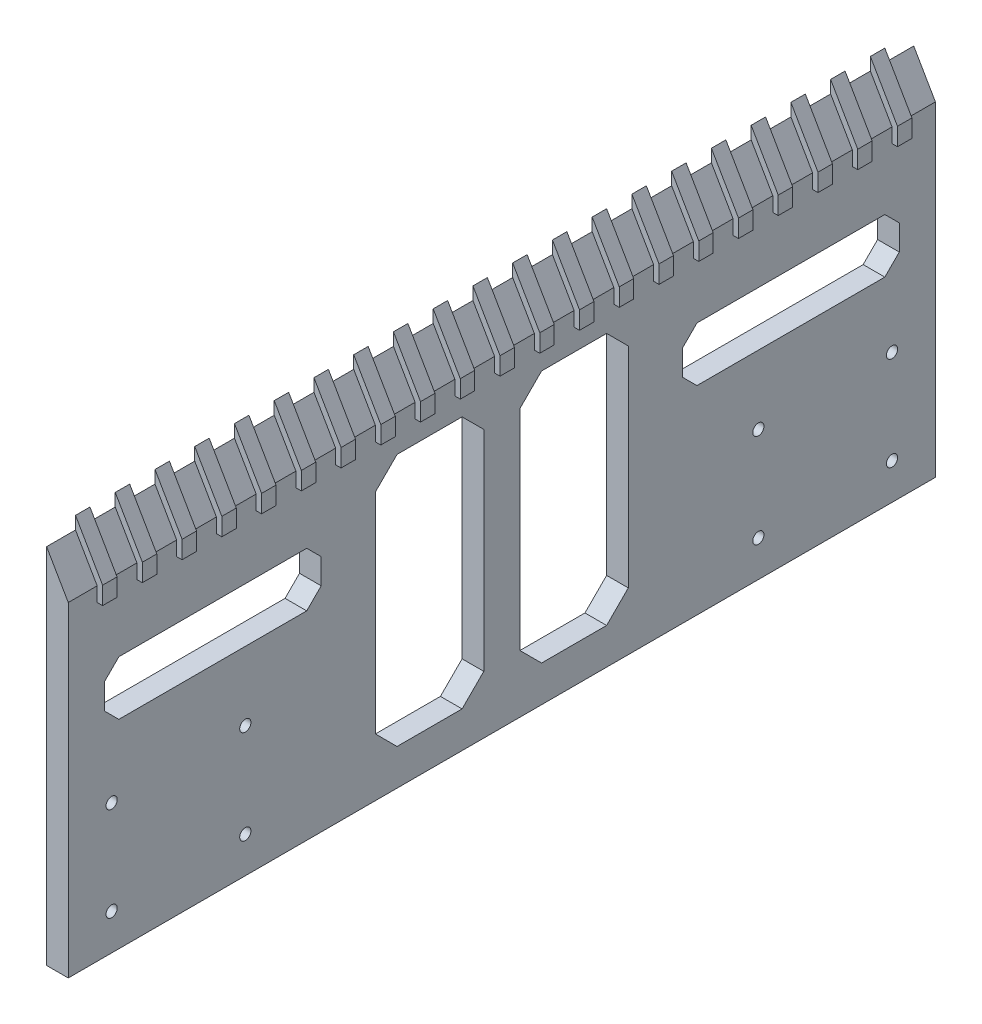
SolidWorks part; units mm, degrees
ref_plane "前视基准面" through (0, 0, 0) normal (0, 0, 1) x (1, 0, 0)
ref_plane "上视基准面" through (0, 0, 0) normal (0, 1, 0) x (1, 0, 0)
ref_plane "右视基准面" through (0, 0, 0) normal (1, 0, 0) x (0, 0, -1)
sketch "草图1" plane through (0, 0, 0) normal (1, 0, 0) x (0, 0, -1)
  line L1 (0, 0) -> (240, 0)
  line L2 (0, 0) -> (0, -90)
  line L3 (0, -90) -> (240, -90)
  line L4 (240, 0) -> (240, -90)
  dimension "D1" = 240
  dimension "D2" = 90
extrude "凸台-拉伸1" add sketch "草图1" along normal blind 6
sketch "草图2" plane through (6, 0, 0) normal (1, 0, 0) x (0, 0, -1)
  line L0 (0, 0) -> (0, -90) construction
  line L1 (12, -54) -> (49, -54) construction
  line L2 (12, -54) -> (12, -80) construction
  line L3 (12, -80) -> (49, -80) construction
  line L4 (49, -54) -> (49, -80) construction
  line L5 (240, 0) -> (0, 0) construction
  line L6 (120, 0) -> (120, -90) construction
  line L7 (0, -90) -> (240, -90) construction
  line L8 (191, -54) -> (191, -80) construction
  line L9 (228, -80) -> (191, -80) construction
  line L10 (228, -54) -> (228, -80) construction
  line L11 (228, -54) -> (191, -54) construction
  circle A0 centre (12, -54) radius 1.55
  circle A1 centre (49, -80) radius 1.55
  circle A2 centre (49, -54) radius 1.55
  circle A3 centre (12, -80) radius 1.55
  circle A4 centre (228, -80) radius 1.55
  circle A5 centre (191, -54) radius 1.55
  circle A6 centre (191, -80) radius 1.55
  circle A7 centre (228, -54) radius 1.55
  dimension "D5" = 3.1
  dimension "D1" = 12
  dimension "D2" = 54
  dimension "D3" = 37
  dimension "D4" = 26
extrude "切除-拉伸1" cut sketch "草图2" against normal through all
sketch "草图3" plane through (6, 0, 0) normal (1, 0, 0) x (0, 0, -1)
  line L0 (120, 0) -> (120, -90) construction
  line L1 (10, -20) -> (70, -20)
  line L2 (10, -20) -> (10, -35)
  line L3 (10, -35) -> (70, -35)
  line L4 (70, -20) -> (70, -35)
  line L5 (240, 0) -> (0, 0) construction
  line L6 (0, -90) -> (240, -90) construction
  line L7 (0, 0) -> (0, -90) construction
  line L8 (170, -20) -> (170, -35)
  line L9 (230, -35) -> (170, -35)
  line L10 (230, -20) -> (230, -35)
  line L11 (230, -20) -> (170, -20)
  dimension "D1" = 10
  dimension "D2" = 20
  dimension "D3" = 15
  dimension "D4" = 60
extrude "切除-拉伸2" cut sketch "草图3" against normal through all
sketch "草图4" plane through (6, 0, 0) normal (1, 0, 0) x (0, 0, -1)
  line L0 (120, 0) -> (120, -90) construction
  line L1 (85, -10) -> (115, -10)
  line L2 (85, -10) -> (85, -80)
  line L3 (85, -80) -> (115, -80)
  line L4 (115, -10) -> (115, -80)
  line L5 (240, 0) -> (0, 0) construction
  line L6 (0, -90) -> (240, -90) construction
  line L7 (0, 0) -> (0, -90) construction
  line L8 (125, -10) -> (125, -80)
  line L9 (155, -80) -> (125, -80)
  line L10 (155, -10) -> (155, -80)
  line L11 (155, -10) -> (125, -10)
  dimension "D1" = 10
  dimension "D2" = 70
  dimension "D3" = 85
  dimension "D4" = 30
extrude "切除-拉伸3" cut sketch "草图4" against normal through all contours L4 L1 L2 L3 | L8 L9 L10 L11 region at (6, -45, -100)
sketch "草图5" plane through (0, 0, 0) normal (-1, 0, 0) x (0, 0, 1)
  circle A0 centre (-191, -80) radius 3
  circle A1 centre (-228, -80) radius 3
  circle A2 centre (-191, -54) radius 3
  circle A3 centre (-228, -54) radius 3
  circle A4 centre (-45, -80) radius 3
  circle A5 centre (-12, -80) radius 3
  circle A6 centre (-12, -54) radius 3
  circle A7 centre (-49, -54) radius 3
  dimension "D1" = 6
extrude "切除-拉伸4" cut sketch "草图5" against normal blind 3
sketch "草图6" plane through (0, 0, 0) normal (0, 0, 1) x (1, 0, 0)
  line L0 (6, 0) -> (0, 0)
  line L1 (0, 0) -> (0, 10.3923)
  line L2 (0, 10.3923) -> (6, 0)
  dimension "D1" = 30
extrude "凸台-拉伸2" add sketch "草图6" against normal blind 240
ref_plane "基准面1" through (0, 0, -120) normal (0, 0, 1) x (1, 0, 0)
chamfer "倒角1" distance 4 angle 45 8 edges at (3, -35, -170) (3, -35, -230) (3, -20, -230) (3, -20, -170) (3, -35, -70) (3, -20, -70) (3, -35, -10) (3, -20, -10)
chamfer "倒角2" distance 6 angle 45 8 edges at (3, -80, -125) (3, -10, -155) (3, -10, -125) (3, -80, -155) (3, -80, -115) (3, -80, -85) (3, -10, -115) (3, -10, -85)
sketch "草图8" plane through (0, 0, -120) normal (0, 0, 1) x (1, 0, 0)
  line L0 (0, 10.3923) -> (0, 13.8923)
  line L1 (0, 13.8923) -> (7.5, 0.9019)
  line L2 (7.5, 0.9019) -> (7.5, -4)
  line L3 (7.5, -4) -> (6, -4)
  line L4 (6, 0) -> (6, -90) construction
  line L5 (6, -4) -> (6, 0)
  line L6 (6, 0) -> (0, 10.3923) construction
  line L7 (6, 0) -> (0, 10.3923)
  point P13 (7.5, 0.4019)
  dimension "D1" = 3.5
  dimension "D2" = 1.5
  dimension "D3" = 4
extrude "凸台-拉伸3" add sketch "草图8" along normal mid plane 4
pattern_linear "阵列(线性)1" count 11 spacing 11 along (0, 0, 1) count 11 spacing 11 along (0, 0, -1) of "凸台-拉伸3"
